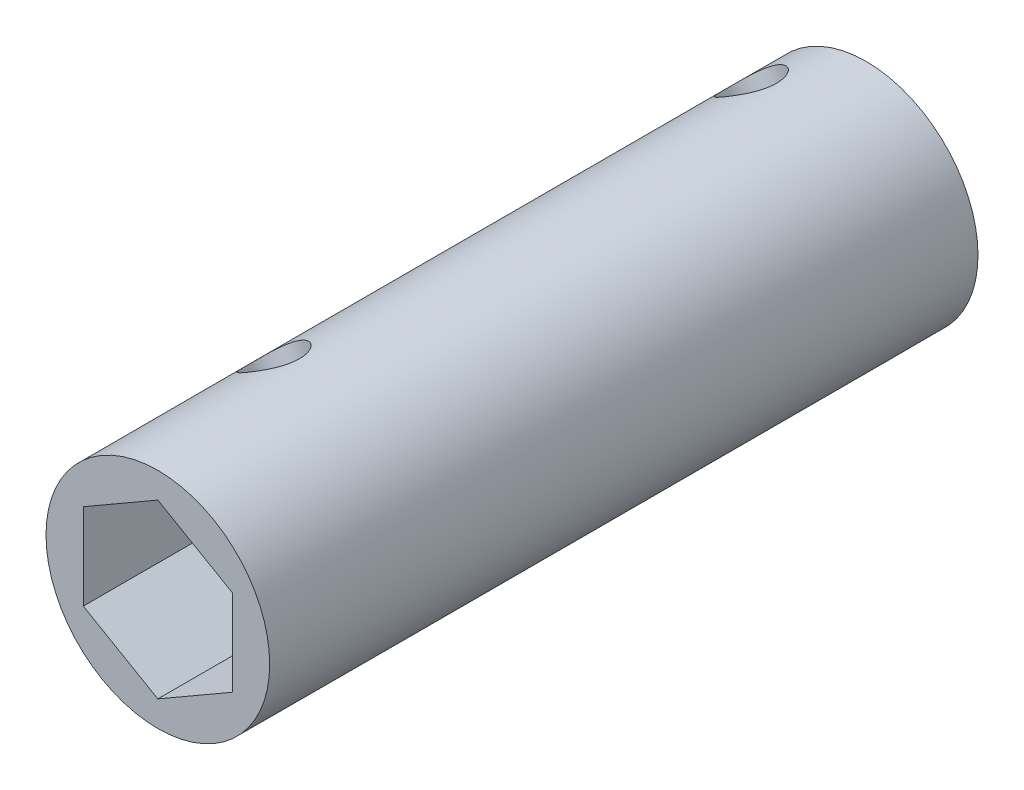
SolidWorks part; units mm, degrees
ref_plane "Front" through (0, 0, 0) normal (0, 0, 1) x (1, 0, 0)
ref_plane "Top" through (0, 0, 0) normal (0, 1, 0) x (1, 0, 0)
ref_plane "Right" through (0, 0, 0) normal (1, 0, 0) x (0, 0, -1)
sketch "Sketch1" plane through (0, 0, 0) normal (0, 0, 1) x (1, 0, 0)
  line L1 (6.35, 3.6662) -> (0, 7.3323)
  line L2 (0, 7.3323) -> (-6.35, 3.6662)
  line L3 (-6.35, 3.6662) -> (-6.35, -3.6662)
  line L4 (-6.35, -3.6662) -> (0, -7.3323)
  line L5 (0, -7.3323) -> (6.35, -3.6662)
  line L6 (6.35, -3.6662) -> (6.35, 3.6662)
  circle A0 centre (0, 0) radius 6.35 construction
  circle A1 centre (0, 0) radius 9.525
  dimension "D2" = 19.05
  dimension "D1" = 12.7
extrude "Boss-Extrude1" add sketch "Sketch1" along normal blind 60.325
ref_plane "Plane1" through (5.08, -8.7988, 0) normal (-0.5, 0.866, 0) x (0.866, 0.5, 0)
sketch "Sketch3" plane through (5.08, -8.7988, 0) normal (-0.5, 0.866, 0) x (0.866, 0.5, 0)
  line L0 (3.6662, 0) -> (-3.6662, 0) construction
  circle A0 centre (0, -5.08) radius 2.3813
  circle A1 centre (0, -45.72) radius 2.3812
  point P6 (0, -5.08)
  point P8 (0, -5.08)
  dimension "D1" = 5.08
  dimension "D3" = 4.7625
  dimension "D2" = 45.72
extrude "Cut-Extrude1" cut sketch "Sketch3" against normal through all both and the other way through all
